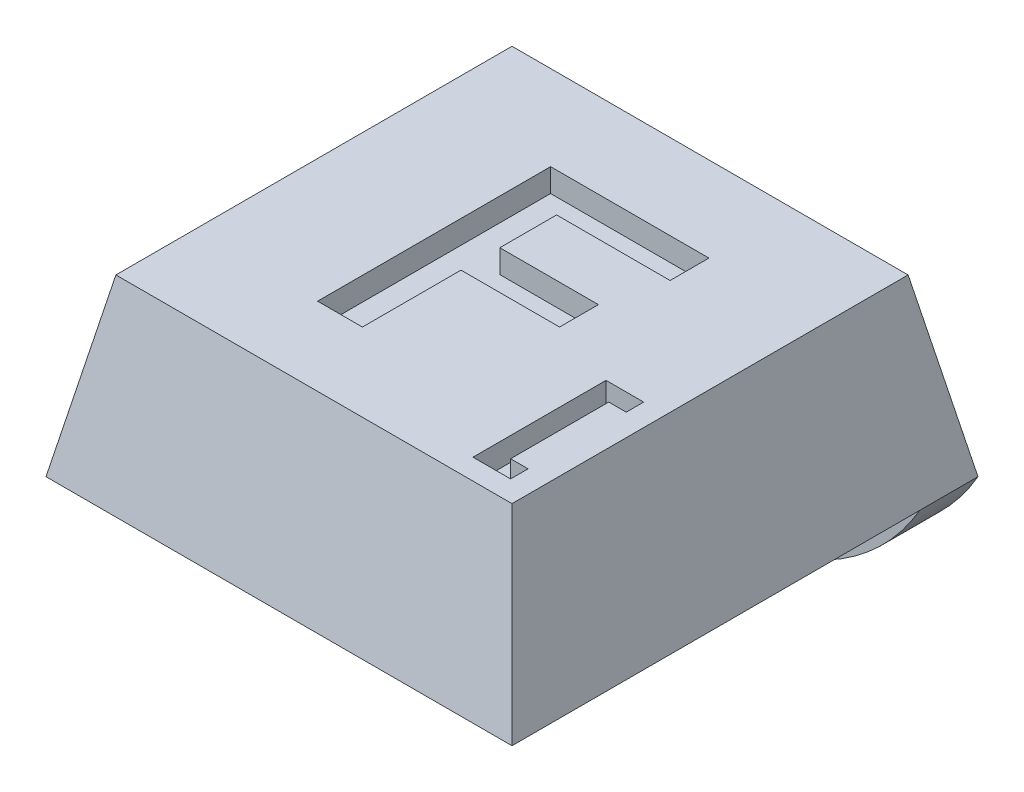
SolidWorks part; units mm, degrees
ref_plane "Front Plane" through (0, 0, 0) normal (0, 0, 1) x (1, 0, 0)
ref_plane "Top Plane" through (0, 0, 0) normal (0, 1, 0) x (1, 0, 0)
ref_plane "Right Plane" through (0, 0, 0) normal (1, 0, 0) x (0, 0, -1)
sketch "Sketch1" plane through (0, 0, 0) normal (0, 1, 0) x (1, 0, 0)
  line L1 (0, 0) -> (8, 0)
  line L2 (0, 0) -> (0, 8)
  line L3 (0, 8) -> (8, 8)
  line L4 (8, 0) -> (8, 8)
  dimension "D1" = 8
  dimension "D2" = 8
extrude "Boss-Extrude1" add sketch "Sketch1" along normal blind 3
sketch "Sketch2" plane through (0, 0, 0) normal (0, 0, 1) x (1, 0, 0)
  line L0 (0, 0) -> (0.6, 3)
  line L1 (0, 3) -> (8, 3) construction
  line L2 (0.6, 3) -> (0, 3)
  line L3 (0, 3) -> (0, 0)
  line L4 (8, 0) -> (7.4, 3)
  line L5 (7.4, 3) -> (8, 3)
  line L6 (8, 3) -> (8, 0)
  dimension "D1" = 0.6
  dimension "D2" = 0.6
extrude "Cut-Extrude1" cut sketch "Sketch2" against normal through all both and the other way through all
sketch "Sketch3" plane through (0, 0, 0) normal (1, 0, 0) x (0, 0, -1)
  line L0 (0, 0) -> (0.6, 3)
  line L1 (8, 3) -> (0, 3) construction
  line L2 (0.6, 3) -> (0, 3)
  line L3 (0, 3) -> (0, 0)
  line L4 (8, 3) -> (7.4, 3)
  line L5 (7.4, 3) -> (8, 0)
  line L6 (8, 3) -> (8, 0)
  dimension "D1" = 0.6
  dimension "D2" = 0.6
extrude "Cut-Extrude2" cut sketch "Sketch3" along normal blind 11
sketch "Sketch4" plane through (0, 0, 0) normal (0, -1, 0) x (1, 0, 0)
  line L0 (8, 0) -> (8, -8) construction
  line L3 (0, 0) -> (8, 0) construction
  circle A0 centre (4, -3.75) radius 1.75
  dimension "D1" = 3.5
  dimension "D2" = 4
  dimension "D3" = 3.75
extrude "Cut-Extrude3" cut sketch "Sketch4" against normal blind 0.4
sketch "Sketch5" plane through (0, 0, 0) normal (0, -1, 0) x (1, 0, 0)
  line L0 (8, 0) -> (8, -8) construction
  line L1 (0, -8) -> (8, -8)
  line L2 (0, -8) -> (0, -7)
  line L3 (0, -7) -> (8, -7)
  line L4 (8, -8) -> (8, -7)
  dimension "D1" = 1
extrude "Boss-Extrude2" add sketch "Sketch5" along normal blind 2
fillet "Fillet1" radius 4 2 edges at (8, -2, -7.5) (0, -2, -7.5)
sketch "Sketch6" plane through (0, 3, 0) normal (0, 1, 0) x (1, 0, 0)
  text T0 "F" font "Arial" height 4
extrude "Cut-Extrude4" cut sketch "Sketch6" against normal blind 0.4
sketch "Sketch7" plane through (0, 3, 0) normal (0, 1, 0) x (1, 0, 0)
  text T0 "[" font "Arial" height 1.8
extrude "Cut-Extrude5" cut sketch "Sketch7" against normal blind 0.4
